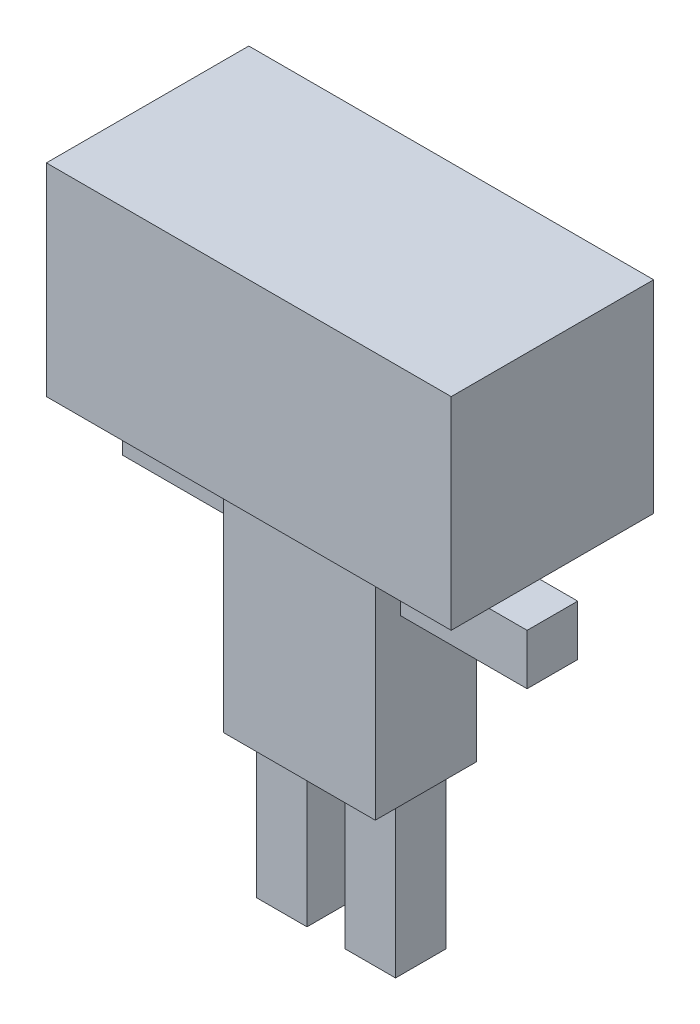
SolidWorks part; units mm, degrees
ref_plane "Front Plane" through (0, 0, 0) normal (0, 0, 1) x (1, 0, 0)
ref_plane "Top Plane" through (0, 0, 0) normal (0, 1, 0) x (1, 0, 0)
ref_plane "Right Plane" through (0, 0, 0) normal (1, 0, 0) x (0, 0, -1)
sketch "Sketch1" plane through (0, 0, 0) normal (0, 0, 1) x (1, 0, 0)
  line L1 (-800, 1300) -> (800, 1300)
  line L2 (-800, 1300) -> (-800, 500)
  line L3 (-800, 500) -> (800, 500)
  line L4 (800, 1300) -> (800, 500)
  dimension "D1" = 800
  dimension "D2" = 1600
  dimension "D3" = 800
  dimension "D4" = 500
extrude "Boss-Extrude1" add sketch "Sketch1" along normal blind 400 and the other way blind 400
sketch "Sketch2" plane through (0, 0, 0) normal (0, 0, 1) x (1, 0, 0)
  line L0 (-800, 500) -> (800, 500) construction
  line L1 (-300, 500) -> (300, 500)
  line L2 (-300, 500) -> (-300, -500)
  line L3 (-300, -500) -> (300, -500)
  line L4 (300, 500) -> (300, -500)
  dimension "D1" = 600
  dimension "D2" = 1000
  dimension "D3" = 300
extrude "Boss-Extrude2" add sketch "Sketch2" along normal blind 200 and the other way blind 200
sketch "Sketch3" plane through (0, 0, 0) normal (0, 0, 1) x (1, 0, 0)
  line L0 (-300, -500) -> (300, -500) construction
  line L1 (-270, -500) -> (-70, -500)
  line L2 (-270, -500) -> (-270, -1100)
  line L3 (-270, -1100) -> (-70, -1100)
  line L4 (-70, -500) -> (-70, -1100)
  line L5 (300, -500) -> (300, 500) construction
  line L6 (80, -500) -> (280, -500)
  line L7 (80, -500) -> (80, -1100)
  line L8 (80, -1100) -> (280, -1100)
  line L9 (280, -500) -> (280, -1100)
  dimension "D1" = 200
  dimension "D2" = 200
  dimension "D3" = 600
  dimension "D4" = 0
  dimension "D5" = 150
  dimension "D6" = 20
extrude "Boss-Extrude3" add sketch "Sketch3" along normal blind 100 and the other way blind 100
sketch "Sketch4" plane through (-300, 0, 0) normal (-1, 0, 0) x (0, 0, 1)
  line L0 (-100, -500) -> (-100, -1100) construction
  line L1 (-100, 350) -> (100, 350)
  line L2 (-100, 350) -> (-100, 150)
  line L3 (-100, 150) -> (100, 150)
  line L4 (100, 350) -> (100, 150)
  line L5 (100, -500) -> (100, -1100) construction
  line L6 (-400, 500) -> (400, 500) construction
  point P8 (0, 500)
  dimension "D1" = 0
  dimension "D2" = 0
  dimension "D3" = 150
  dimension "D4" = 200
extrude "Boss-Extrude4" add sketch "Sketch4" along normal blind 500
mirror "Mirror1" about plane through (0, 0, 0) normal (1, 0, 0) of "Boss-Extrude4"
sketch "Sketch5" plane through (0, 0, -400) normal (0, 0, -1) x (-1, 0, 0)
  line L0 (0, 800) -> (-141.4214, 658.5786)
  line L1 (-141.4214, 658.5786) -> (141.4214, 658.5786)
  line L2 (141.4214, 658.5786) -> (0, 800)
  line L3 (800, 500) -> (-800, 500) construction
  circle A0 centre (-300, 1000) radius 100
  circle A1 centre (300, 1000) radius 100
  dimension "D6" = 200
  dimension "D7" = 200
  dimension "D1" = 200
  dimension "D2" = 200
  dimension "D3" = 0
  dimension "D4" = 600
  dimension "D5" = 300
  dimension "D8" = 500
  dimension "D9" = 500
  dimension "D10" = 300
extrude "Boss-Extrude5" add sketch "Sketch5" along normal blind 100
